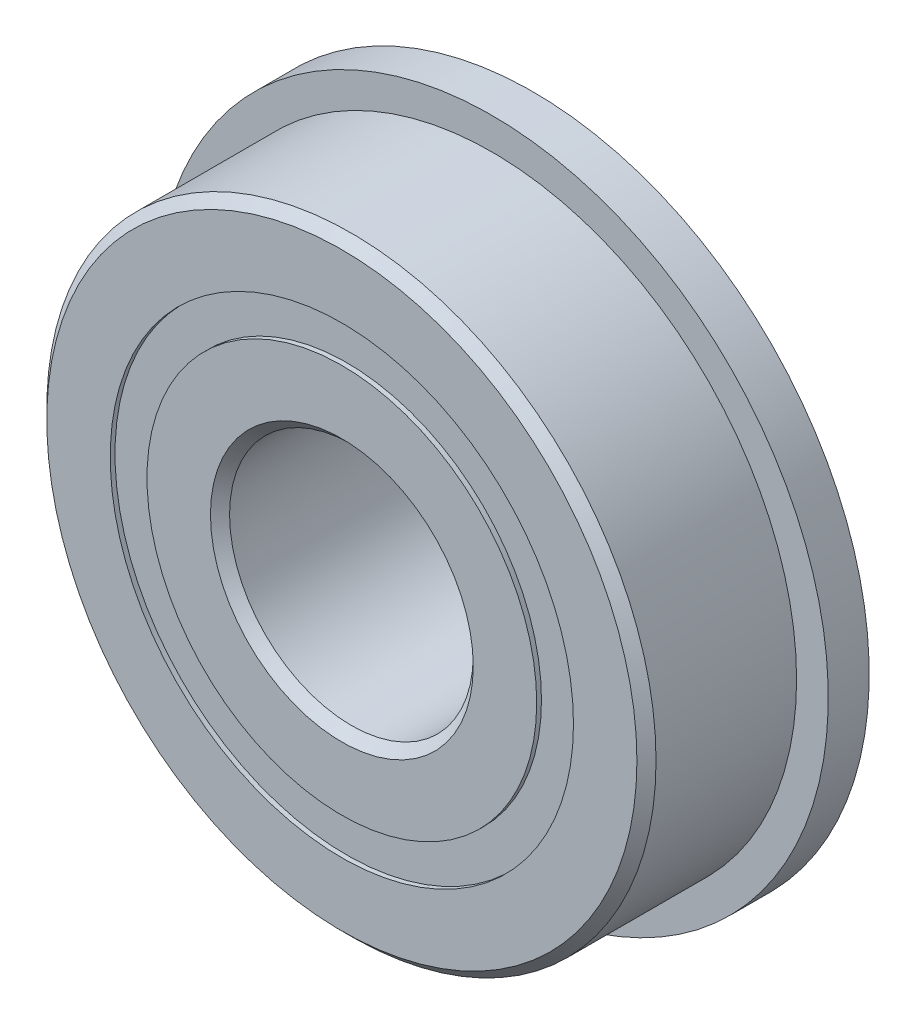
SolidWorks part; units mm, degrees
material "AISI 304"
ref_plane "Front Plane" through (0, 0, 0) normal (0, 0, 1) x (1, 0, 0)
ref_plane "Top Plane" through (0, 0, 0) normal (0, 1, 0) x (1, 0, 0)
ref_plane "Right Plane" through (0, 0, 0) normal (1, 0, 0) x (0, 0, -1)
sketch "Sketch1" plane through (0, 0, 0) normal (1, 0, 0) x (0, 0, -1)
  line L0 (-2.4892, 0) -> (2.4892, 0) construction
  line L1 (0, 7.9375) -> (0, -7.9375) construction
  line L2 (2.2403, 7.9375) -> (-2.2403, 7.9375)
  line L3 (-2.2403, 7.9375) -> (-2.4892, 7.6886)
  line L4 (-2.4892, 7.6886) -> (-2.4892, 6.0352)
  line L5 (-2.4892, 6.0352) -> (-1.1063, 6.0352)
  line L6 (2.4892, 6.0352) -> (1.1063, 6.0352)
  line L7 (2.4892, 7.6886) -> (2.4892, 6.0352)
  line L8 (2.2403, 7.9375) -> (2.4892, 7.6886)
  line L9 (0, 7.9375) -> (0, 5.5563) construction
  line L10 (0, 5.5563) -> (0, 3.175) construction
  arc A0 (-1.1063, 6.0352) -> (1.1063, 6.0352) centre (0, 5.5563) cw
  point P14 (0, 3.175)
  dimension "D3" = 2.2126
  dimension "D1" = 45
  dimension "Width" = 4.9784
  dimension "OD" = 15.875
  dimension "D2" = 0.2489
  dimension "Shaft Dia" = 6.35
  dimension "D4" = 0.479
revolve "Revolve1" add sketch "Sketch1" angle 360 about L0
sketch "Sketch3" plane through (0, 0, 0) normal (1, 0, 0) x (0, 0, -1)
  line L0 (-2.4892, 5.0773) -> (-1.1063, 5.0773)
  line L1 (0, 7.9375) -> (0, -7.9375) construction
  line L2 (-2.4892, 7.6886) -> (-2.4892, 6.0352) construction
  line L3 (-2.4892, 5.0773) -> (-2.4892, 3.4239)
  line L4 (-2.2403, 7.9375) -> (-2.4892, 7.6886) construction
  line L5 (-2.4892, 3.4239) -> (-2.2403, 3.175)
  line L6 (-2.2403, 3.175) -> (2.2403, 3.175)
  line L7 (2.2403, 7.9375) -> (2.2403, -7.9375) construction
  line L8 (2.2403, 3.175) -> (2.4892, 3.4239)
  line L9 (2.4892, -7.6886) -> (2.4892, 7.6886) construction
  line L10 (2.4892, 3.4239) -> (2.4892, 5.0773)
  line L11 (2.4892, 5.0773) -> (1.1063, 5.0773)
  line L13 (2.2403, 7.9375) -> (2.4892, 7.6886) construction
  arc A0 (1.1063, 6.0352) -> (-1.1063, 6.0352) centre (0, 5.5563) ccw construction
  arc A1 (1.1063, 5.0773) -> (-1.1063, 5.0773) centre (0, 5.5562) cw
revolve "Revolve3" add sketch "Sketch3" angle 360 about L0
sketch "Sketch4" plane through (0, 0, 0) normal (1, 0, 0) x (0, 0, -1)
  line L0 (-1.2055, 5.5563) -> (1.2055, 5.5563)
  arc A2 (-1.2055, 5.5563) -> (1.2055, 5.5563) centre (0, 5.5563) cw
  arc A3 (1.1063, 6.0352) -> (-1.1063, 6.0352) centre (0, 5.5563) ccw construction
revolve "Revolve4" add sketch "Sketch4" angle 360 about L0
ref_axis "Axis1" through (0, 0, -2.4892) along (0, 0, 1)
pattern_circular "CirPattern1" count 12 every 30 about axis through (0, 0, -2.4892) along (0, 0, 1) of bodies 104
sketch "Sketch5" plane through (0, 0, 0) normal (1, 0, 0) x (0, 0, -1)
  line L0 (-2.4892, 6.0352) -> (-1.1063, 6.0352) construction
  line L1 (-2.3647, 6.0352) -> (-1.2055, 6.0352)
  line L2 (-2.3647, 6.0352) -> (-2.3647, 5.0773)
  line L3 (-2.3647, 5.0773) -> (-1.2055, 5.0773)
  line L4 (-1.2055, 6.0352) -> (-1.2055, 5.0773)
  line L5 (-2.4892, 5.0773) -> (-1.1063, 5.0773) construction
  line L6 (2.4892, 6.0352) -> (1.1063, 6.0352) construction
  line L7 (2.3647, 6.0352) -> (1.2055, 6.0352)
  line L8 (2.3647, 6.0352) -> (2.3647, 5.0773)
  line L9 (2.3647, 5.0773) -> (1.2055, 5.0773)
  line L10 (1.2055, 6.0352) -> (1.2055, 5.0773)
  line L11 (2.4892, 5.0773) -> (1.1063, 5.0773) construction
  line L12 (-2.2403, 7.9375) -> (-2.4892, 7.6886) construction
  point P18 (-2.3647, 7.813)
revolve "Revolve5" add sketch "Sketch5" angle 360 about L0
sketch "Sketch6" plane through (0, 0, 0) normal (1, 0, 0) x (0, 0, -1)
  line L0 (2.4892, 0) -> (-2.4892, 0) construction
  line L1 (2.4892, 6.0352) -> (1.4224, 6.0352)
  line L2 (2.4892, 6.0352) -> (2.4892, 8.763)
  line L3 (2.4892, 8.763) -> (1.4224, 8.763)
  line L4 (1.4224, 6.0352) -> (1.4224, 8.763)
  dimension "Th" = 1.0668
  dimension "Flange OD" = 17.526
revolve "Revolve6" add sketch "Sketch6" angle 360 about L0
equation "\"D2@Sketch1\" = \"Width@Sketch1\"*.05"
equation "\"D3@Sketch1\" = \"Width@Sketch1\"/2.25"
equation "\"D4@Sketch1\" = (((\"OD@Sketch1\"-\"Width@Sketch1\")/2)/3.25)/3.5"
equation "\"D2@CirPattern1\" = 360/\"Balls@CirPattern1\""
